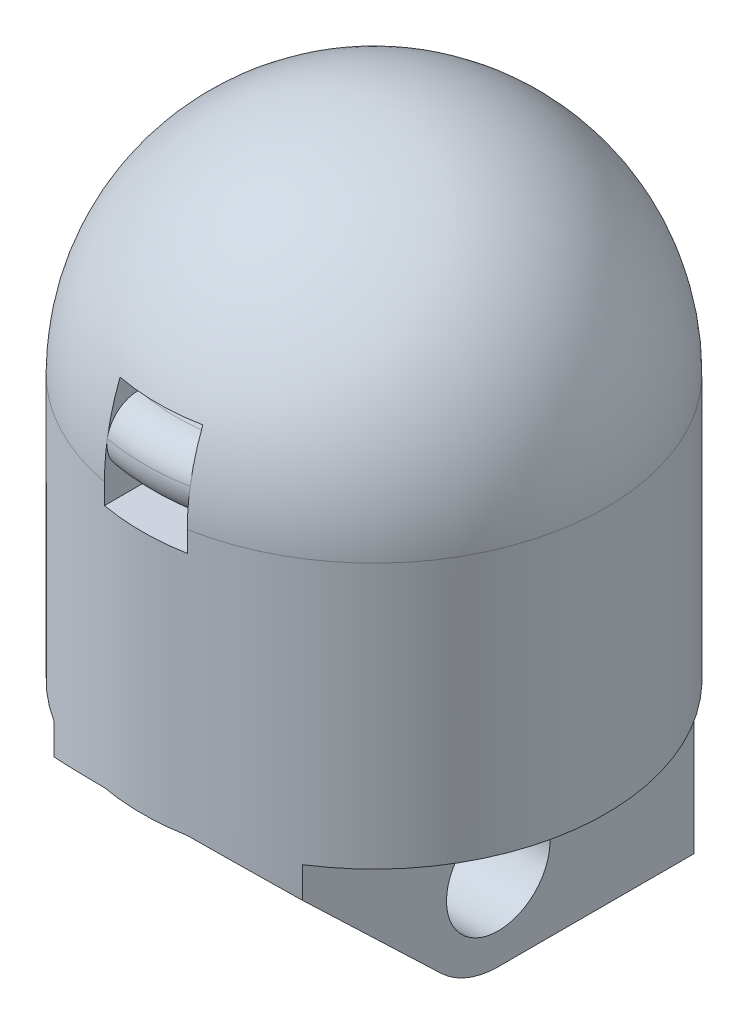
SolidWorks part; units mm, degrees
ref_plane "Front Plane" through (0, 0, 0) normal (0, 0, 1) x (1, 0, 0)
ref_plane "Top Plane" through (0, 0, 0) normal (0, 1, 0) x (1, 0, 0)
ref_plane "Right Plane" through (0, 0, 0) normal (1, 0, 0) x (0, 0, -1)
sketch "Sketch1" plane through (0, 0, 0) normal (0, 0, 1) x (1, 0, 0)
  line L0 (0, 0) -> (0, 5.6026)
  line L1 (0, 0) -> (-14.224, 0)
  line L2 (-14.224, 0) -> (-14.224, 27.686)
  line L6 (0, 5.6026) -> (-2.54, 5.6026)
  line L7 (-2.54, 22.86) -> (-2.54, 5.6026)
  line L8 (0, 33.1396) -> (0, 41.91)
  arc A0 (0, 41.91) -> (-14.224, 27.686) centre (0, 27.686) ccw
  arc A1 (-2.54, 22.86) -> (0, 33.1396) centre (0, 27.686) cw
  dimension "D3" = 28.448
  dimension "D1" = 41.91
  dimension "D2" = 14.224
  dimension "D4" = 2.54
revolve "Revolve1" add sketch "Sketch1" angle 360 about L0
sketch "Sketch2" plane through (0, 0, 0) normal (0, -1, 0) x (1, 0, 0)
  line L0 (-2.54, 13.9954) -> (-2.54, -13.9954)
  line L1 (-7.62, 12.0107) -> (-7.62, -12.0107)
  line L2 (2.54, 13.9954) -> (2.54, -13.9954)
  line L3 (7.62, 12.0107) -> (7.62, -12.0107)
  circle A0 centre (0, 0) radius 14.224 construction
  arc A1 (-7.62, 12.0107) -> (-7.62, -12.0107) centre (0, 0) ccw
  arc A2 (-2.54, -13.9954) -> (2.54, -13.9954) centre (0, 0) ccw
  arc A3 (7.62, -12.0107) -> (7.62, 12.0107) centre (0, 0) ccw
  arc A4 (2.54, 13.9954) -> (-2.54, 13.9954) centre (0, 0) ccw
  dimension "D1" = 2.54
  dimension "D2" = 5.08
  dimension "D3" = 2.54
  dimension "D4" = 5.08
extrude "Cut-Extrude1" cut sketch "Sketch2" against normal blind 11.43
sketch "Sketch3" plane through (-7.62, 0, 0) normal (-1, 0, 0) x (0, 0, 1)
  line L0 (0, -15.6464) -> (0, 15.6464) construction
  line L1 (-12.0107, 0) -> (12.0107, 0) construction
  line L2 (3.5101, 1.4077) -> (13.9954, 11.43)
  line L3 (13.9954, 11.43) -> (13.9954, 0)
  line L4 (13.9954, 0) -> (0, 0)
  circle A0 centre (0, 5.08) radius 3.175
  arc A1 (0, 0) -> (3.5101, 1.4077) centre (0, 5.08) ccw
  dimension "D2" = 6.35
  dimension "D1" = 5.08
extrude "Cut-Extrude2" cut sketch "Sketch3" against normal through all
sketch "Sketch4" plane through (0, 0, 0) normal (0, 0, 1) x (1, 0, 0)
  line L0 (14.224, 27.686) -> (-14.224, 27.686) construction
  line L1 (-2.54, 27.686) -> (2.54, 27.686)
  line L2 (-2.54, 27.686) -> (-2.54, 26.416)
  line L3 (-2.54, 26.416) -> (2.54, 26.416)
  line L4 (2.54, 27.686) -> (2.54, 26.416)
  line L6 (-2.54, 31.496) -> (2.54, 31.496)
  line L7 (-2.54, 31.496) -> (-2.54, 32.766)
  line L8 (-2.54, 32.766) -> (2.54, 32.766)
  line L9 (2.54, 31.496) -> (2.54, 32.766)
  point P10 (0, 26.416)
  dimension "D1" = 1.27
  dimension "D2" = 1.27
  dimension "D3" = 3.81
extrude "Cut-Extrude3" cut sketch "Sketch4" against normal through all both and the other way through all
fillet "Fillet1" radius 1.905 4 edges at (0, 27.686, -14.224) (0, 31.496, -13.7042) (0, 27.686, 14.224) (0, 31.496, 13.7042)
